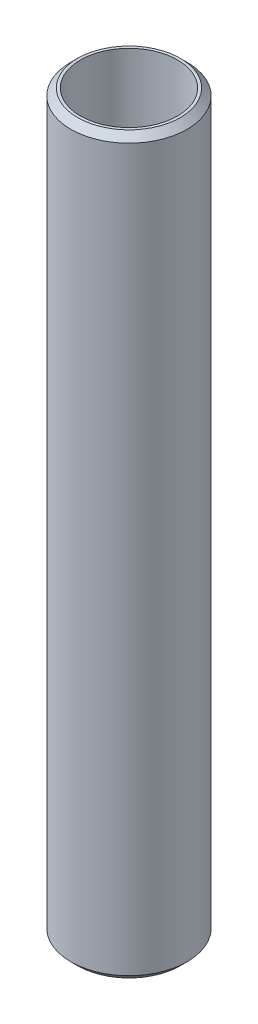
SolidWorks part; units mm, degrees
ref_plane "Front Plane" through (0, 0, 0) normal (0, 0, 1) x (1, 0, 0)
ref_plane "Top Plane" through (0, 0, 0) normal (0, 1, 0) x (1, 0, 0)
ref_plane "Right Plane" through (0, 0, 0) normal (1, 0, 0) x (0, 0, -1)
sketch "Sketch1" plane through (0, 0, 0) normal (0, 1, 0) x (1, 0, 0)
  circle A0 centre (0, 0) radius 47.5
  dimension "SHAFT_OD" = 95
extrude "Boss-Extrude1" add sketch "Sketch1" along normal blind 600
sketch "Sketch2" plane through (0, 0, 0) normal (0, 1, 0) x (1, 0, 0)
  circle A0 centre (0, 0) radius 39.6805
  dimension "BORE_D" = 79.3611
extrude "Cut-Extrude1" cut sketch "Sketch2" along normal through all
chamfer "Chamfer1" distance 5.5273 angle 45 2 edges at (0, 600, 47.5) (0, 0, 47.5)
